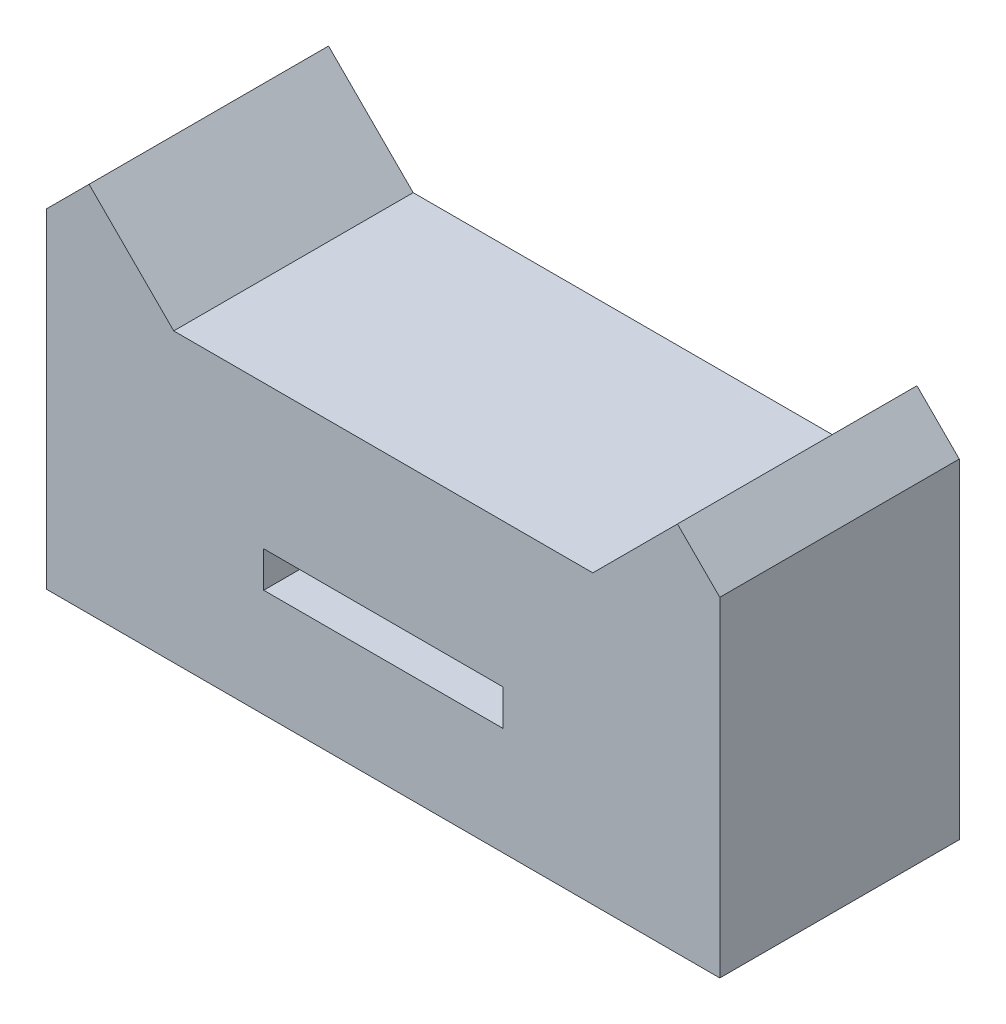
SolidWorks part; units mm, degrees
material "6061 Alloy"
ref_plane "Front Plane" through (0, 0, 0) normal (0, 0, 1) x (1, 0, 0)
ref_plane "Top Plane" through (0, 0, 0) normal (0, 1, 0) x (1, 0, 0)
ref_plane "Right Plane" through (0, 0, 0) normal (1, 0, 0) x (0, 0, -1)
sketch "Sketch2" plane through (0, 0, 0) normal (0, 0, 1) x (1, 0, 0)
  line L0 (0, 0) -> (0, -21)
  line L1 (0, -21) -> (17.5, -21)
  line L2 (17.5, -21) -> (24.5711, -13.9289)
  line L3 (0, -21) -> (-17.5, -21)
  line L4 (-17.5, -21) -> (-24.5711, -13.9289)
  line L5 (0, -21) -> (0, -45)
  line L6 (-17.5, -21) -> (-17.5, -45)
  line L7 (-17.5, -45) -> (0, -45)
  line L8 (0, -45) -> (17.5, -45)
  line L9 (17.5, -45) -> (17.5, -21)
  line L10 (-24.5711, -13.9289) -> (-28.1066, -17.4645)
  line L11 (-28.1066, -17.4645) -> (-28.1066, -45)
  line L12 (-28.1066, -45) -> (-17.5, -45)
  line L13 (24.5711, -13.9289) -> (28.1066, -17.4645)
  line L14 (28.1066, -17.4645) -> (28.1066, -45)
  line L15 (28.1066, -45) -> (17.5, -45)
  dimension "D1" = 21
  dimension "D2" = 17.5
  dimension "D3" = 10
  dimension "D4" = 135
  dimension "D5" = 17.5
  dimension "D6" = 10
  dimension "D7" = 135
  dimension "D8" = 24
  dimension "D9" = 27.5355
  dimension "D10" = 27.5355
  dimension "D11" = 5
extrude "Boss-Extrude1" add sketch "Sketch2" along normal blind 10 and the other way blind 10 contours L8 L9 L1 L5 | L6 L7 L5 L3 | L15 L14 L13 L2 L9 | L11 L12 L6 L4 L10 region at (-8.75, -33, 0) region at (8.75, -33, 0) region at (22.9638, -30.8697, 0) region at (-22.9638, -30.8697, 0)
sketch "Sketch3" plane through (0, 0, -10) normal (0, 0, -1) x (-1, 0, 0)
  line L0 (0, 0) -> (0, -45)
  line L1 (28.1066, -45) -> (-28.1066, -45) construction
  line L2 (0, -45) -> (0, -33)
  line L3 (0, -33) -> (10, -33)
  line L4 (10, -33) -> (10, -36)
  line L5 (10, -36) -> (0, -36)
  line L6 (0, -36) -> (-9.9848, -36)
  line L7 (-9.9848, -36) -> (-9.9848, -33)
  line L8 (-9.9848, -33) -> (0, -33)
  line L9 (17.5, -21) -> (-17.5, -21) construction
  dimension "D1" = 3
  dimension "D2" = 10
  dimension "D3" = 9.9848
  dimension "D4" = 15
extrude "Cut-Extrude1" cut sketch "Sketch3" against normal blind 10 contours L8 L7 L6 L0 | L5 L4 L3 L0 region at (-5, -34.5, -10) region at (4.9924, -34.5, -10)
move or copy body "Body-Move/Copy1" bodies to move or copy 103 copy no rotation origin (0, 0, 0) rotation axis (0, 1, 0) rotation angle 180
